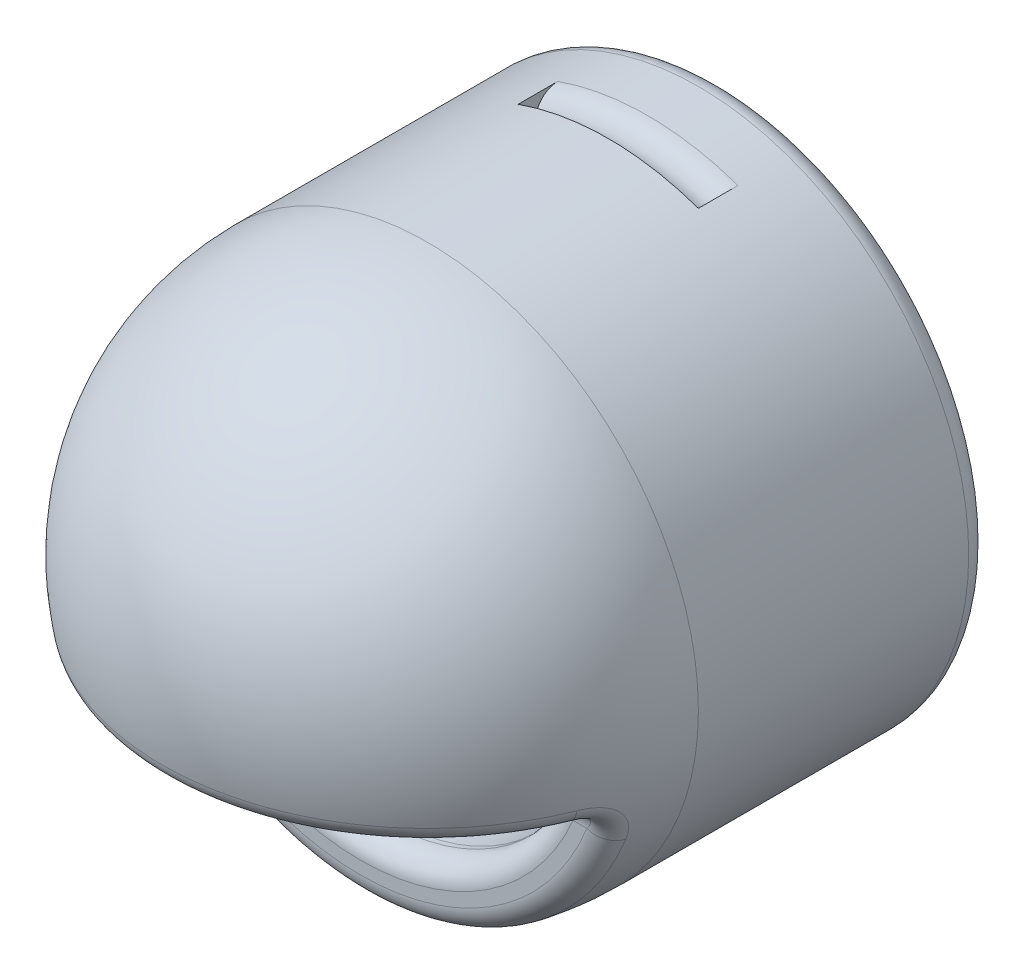
SolidWorks part; units mm, degrees
ref_plane "Front Plane" through (0, 0, 0) normal (0, 0, 1) x (1, 0, 0)
ref_plane "Top Plane" through (0, 0, 0) normal (0, 1, 0) x (1, 0, 0)
ref_plane "Right Plane" through (0, 0, 0) normal (1, 0, 0) x (0, 0, -1)
sketch "Sketch1" plane through (0, 0, 0) normal (0, 0, 1) x (1, 0, 0)
  circle A0 centre (0, 0) radius 12
extrude "Boss-Extrude1" add sketch "Sketch1" along normal blind 25 contours A0
sketch "Sketch2" plane through (0, 0, 0) normal (0, 0, -1) x (-1, 0, 0)
  circle A0 centre (0, 0) radius 9.25
extrude "Cut-Extrude1" cut sketch "Sketch2" against normal blind 24 contours A0
fillet "Fillet1" radius 12 1 edges at (12, 0, 25)
fillet "Fillet2" radius 9.25 1 edges at (-9.25, 0, 24)
fillet "Fillet3" radius 1 1 edges at (-9.25, 0, 0)
sketch "Sketch5" plane through (0, 0, 0) normal (0, 0, -1) x (-1, 0, 0)
  line L3 (5.5, 9) -> (-5.5, 9)
  line L4 (5.5, 9) -> (5.5, 5.5)
  line L5 (5.5, 5.5) -> (-5.5, 5.5)
  line L6 (-5.5, 9) -> (-5.5, 5.5)
extrude "Cut-Extrude5" cut sketch "Sketch5" against normal blind 16
sketch "Sketch6" plane through (0, 9, 0) normal (0, -1, 0) x (1, 0, 0)
  line L0 (0, 5) -> (4, 5)
  line L1 (4, 5) -> (4, 4.2428)
  line L2 (4, 4.2428) -> (-4, 4.2428)
  line L3 (-4, 4.2428) -> (-4, 5)
  line L4 (-4, 5) -> (0, 5)
extrude "Cut-Extrude7" cut sketch "Sketch6" against normal mid plane 52
fillet "Fillet6" radius 1 2 edges at (-3.068, 9, 4.2428) (3.068, 9, 4.2428)
fillet "Fillet7" radius 1 1 edges at (0, 12, 4.2428)
fillet "Fillet8" radius 1 1 edges at (0, -9.25, 4.2428)
fillet "Fillet9" radius 1 1 edges at (0, -12, 4.2428)
fillet "Fillet10" radius 1 1 edges at (12, 0, 0)
sketch3d "3DSketch4"
  line L1 (13.7989, -3, 16) -> (13.7989, -3, 25.3954)
  line L2 (13.7989, -3, 16) -> (-14.0618, -3, 16)
  line L3 (-14.0618, -3, 16) -> (-14.0618, -3, 25.3954)
  line L4 (13.7989, -3, 25.3954) -> (-14.0618, -3, 25.3954)
  point P4 (0, 0, 0)
  point P5 (0, 0, 0)
  point P6 (0, 0, 0)
  point P7 (0, 0, 0)
  point P8 (0, 0, 0)
  point P9 (0, 0, 0)
  point P10 (0, 0, 0)
extrude "Cut-Extrude8" cut sketch "3DSketch4" along direction (0, 1, 0) on the side of the normal blind 10
fillet "Fillet11" radius 1 6 edges at (0, -3, 24.619) (0, -3, 23.5) (0, -11.619, 16) (0, -9.1652, 16)
